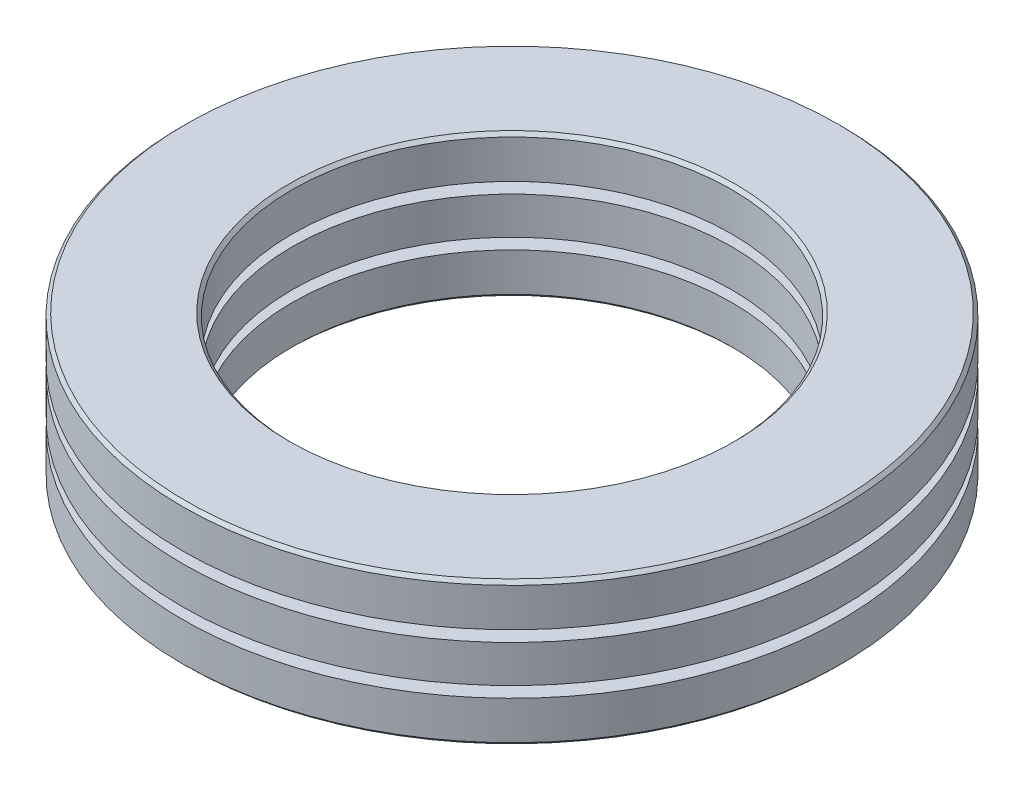
SolidWorks part; units mm, degrees
ref_plane "Front Plane" through (0, 0, 0) normal (0, 0, 1) x (1, 0, 0)
ref_plane "Top Plane" through (0, 0, 0) normal (0, 1, 0) x (1, 0, 0)
ref_plane "Right Plane" through (0, 0, 0) normal (1, 0, 0) x (0, 0, -1)
sketch "Sketch1" plane through (0, 0, 0) normal (0, 1, 0) x (1, 0, 0)
  circle A0 centre (0, 0) radius 20
  circle A1 centre (0, 0) radius 30
  dimension "D1" = 40
  dimension "D2" = 60
extrude "Boss-Extrude1" add sketch "Sketch1" along normal blind 3.8
ref_plane "Plane1" through (0, 4.8, 0) normal (0, 1, 0) x (1, 0, 0)
sketch "Sketch2" plane through (0, 4.8, 0) normal (0, 1, 0) x (1, 0, 0)
  circle A0 centre (0, 0) radius 20 construction
  circle A1 centre (0, 0) radius 30
  circle A2 centre (0, 0) radius 30
  circle A3 centre (0, 0) radius 20
  dimension "D1" = 0
extrude "Boss-Extrude2" add sketch "Sketch2" along normal blind 3.4 separate body
ref_plane "Plane2" through (0, 13, 0) normal (0, -1, 0) x (-1, 0, 0)
sketch "Sketch3" plane through (0, 13, 0) normal (0, -1, 0) x (-1, 0, 0)
  circle A0 centre (0, 0) radius 20 construction
  circle A1 centre (0, 0) radius 30
  circle A2 centre (0, 0) radius 30
  circle A3 centre (0, 0) radius 20
  dimension "D1" = 0
extrude "Boss-Extrude3" add sketch "Sketch3" along normal blind 3.8 separate body
sketch "Sketch4" plane through (0, 0, 0) normal (0, 0, 1) x (1, 0, 0)
  line L0 (-27.7, 6.5) -> (-22.3, 6.5)
  arc A0 (-22.3, 6.5) -> (-27.7, 6.5) centre (-25, 6.5) ccw
  dimension "D1" = 5.4
  dimension "D2" = 25
  dimension "D3" = 6.5
revolve "Cut-Revolve2" cut sketch "Sketch4" angle 360 about L0 region at (-25, 7.6459, 0)
pattern_circular "CirPattern1" count 18 over 360 about axis through (0, 9.2, 0) along (0, 1, 0) of "Cut-Revolve2"
revolve "Revolve1" add sketch "Sketch4<3>" angle 360 about L0
sketch "Sketch4<3>" plane through (0, 0, 0) normal (0, 0, 1) x (1, 0, 0) same geometry as "Sketch4"
pattern_circular "CirPattern4" count 18 over 360 about axis through (0, 9.2, 0) along (0, 1, 0) reverse direction yes of bodies 108
chamfer "Chamfer1" distance 0.3 angle 45 2 edges at (0, 0, 30) (0, 0, 20)
chamfer "Chamfer2" distance 0.3 angle 45 2 edges at (0, 13, -30) (0, 13, -20)
